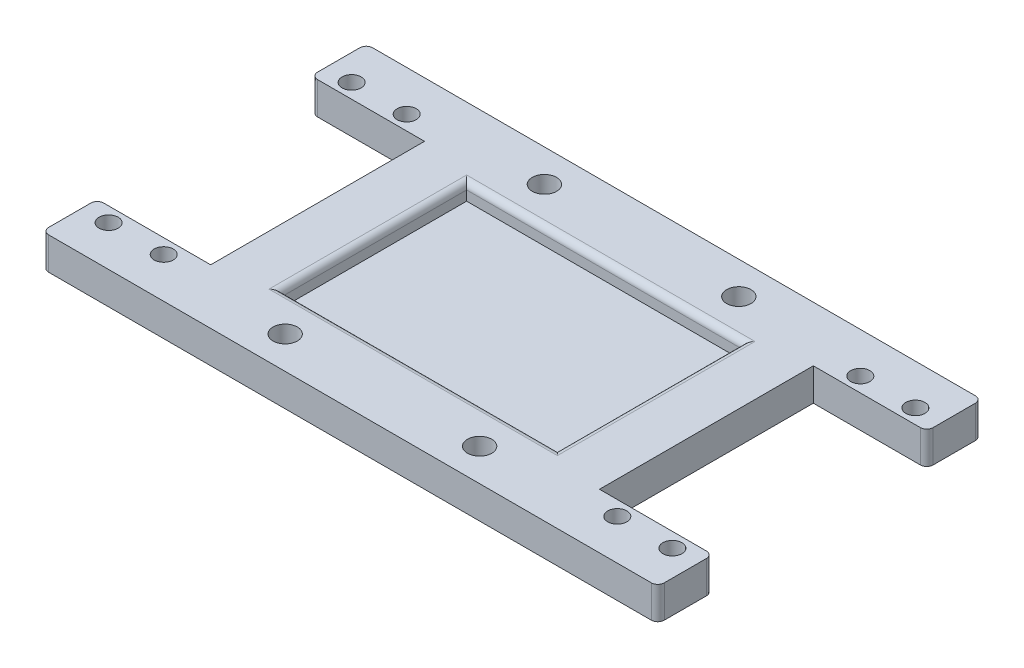
SolidWorks part; units mm, degrees
ref_plane "Front Plane" through (0, 0, 0) normal (0, 0, 1) x (1, 0, 0)
ref_plane "Top Plane" through (0, 0, 0) normal (0, 1, 0) x (1, 0, 0)
ref_plane "Right Plane" through (0, 0, 0) normal (1, 0, 0) x (0, 0, -1)
sketch "Sketch1" plane through (0, 0, 0) normal (0, 1, 0) x (1, 0, 0)
  line L1 (-60, -50) -> (60, -50)
  line L2 (-60, -50) -> (-60, 50)
  line L3 (-60, 50) -> (60, 50)
  line L4 (60, -50) -> (60, 50)
  line L5 (-60, -50) -> (60, 50) construction
  line L6 (-60, 50) -> (60, -50) construction
  point P0 (0, 0)
  dimension "D1" = 100
  dimension "D2" = 120
extrude "Boss-Extrude1" add sketch "Sketch1" along normal blind 5
sketch "Sketch2" plane through (0, 5, 0) normal (0, 1, 0) x (1, 0, 0)
  line L1 (-42.5, -28.5) -> (42.5, -28.5)
  line L2 (-42.5, -28.5) -> (-42.5, 28.5)
  line L3 (-42.5, 28.5) -> (42.5, 28.5)
  line L4 (42.5, -28.5) -> (42.5, 28.5)
  line L5 (-42.5, -28.5) -> (42.5, 28.5) construction
  line L6 (-42.5, 28.5) -> (42.5, -28.5) construction
  line L7 (-60, -50) -> (60, -50)
  line L8 (-60, -50) -> (-60, 50)
  line L9 (-60, 50) -> (60, 50)
  line L10 (60, -50) -> (60, 50)
  line L11 (-60, -50) -> (60, 50) construction
  line L12 (-60, 50) -> (60, -50) construction
  point P0 (0, 0)
  point P6 (0, 0)
  dimension "D1" = 85
  dimension "D2" = 57
extrude "Boss-Extrude2" add sketch "Sketch2" along normal blind 5
sketch "Sketch3" plane through (0, 0, 0) normal (0, -1, 0) x (1, 0, 0)
  line L0 (0, -55) -> (0, 55) construction
  line L1 (60, 50) -> (95, 50)
  line L2 (60, 50) -> (60, 33)
  line L3 (60, 33) -> (95, 33)
  line L4 (95, 50) -> (95, 33)
  line L5 (60, -50) -> (95, -50)
  line L6 (60, -50) -> (60, -33)
  line L7 (60, -33) -> (95, -33)
  line L8 (95, -50) -> (95, -33)
  line L9 (-95, -50) -> (-95, -33)
  line L10 (-60, -33) -> (-95, -33)
  line L11 (-60, -50) -> (-60, -33)
  line L12 (-60, -50) -> (-95, -50)
  line L13 (-95, 50) -> (-95, 33)
  line L14 (-60, 33) -> (-95, 33)
  line L15 (-60, 50) -> (-60, 33)
  line L16 (-60, 50) -> (-95, 50)
  dimension "D1" = 66
  dimension "D2" = 35
extrude "Boss-Extrude3" add sketch "Sketch3" against normal up to surface (10 mm away) up to face at (0, 10, 0)
sketch "Sketch4" plane through (0, 0, 0) normal (0, -1, 0) x (1, 0, 0)
  line L0 (70, 37.5) -> (70, -37.5) construction
  line L1 (60, 33) -> (60, -33) construction
  line L2 (0, -5.5) -> (0, 5.5) construction
  line L3 (-70, 37.5) -> (-70, -37.5) construction
  circle A0 centre (70, 37.5) radius 2.95
  circle A1 centre (87, 37.5) radius 2.95
  circle A2 centre (70, -37.5) radius 2.95
  circle A3 centre (87, -37.5) radius 2.95
  circle A4 centre (-87, -37.5) radius 2.95
  circle A5 centre (-70, -37.5) radius 2.95
  circle A6 centre (-87, 37.5) radius 2.95
  circle A7 centre (-70, 37.5) radius 2.95
  point P8 (70, 0)
  dimension "D3" = 5.9
  dimension "D1" = 75
  dimension "D2" = 17
  dimension "D4" = 10
extrude "Cut-Extrude1" cut sketch "Sketch4" against normal through all both and the other way through all
fillet "Fillet1" radius 2 12 edges at (42.5, 10, 0) (0, 10, -28.5) (-42.5, 10, 0) (0, 10, 28.5) (-95, 5, 50) (-95, 5, 33) (-95, 5, -33) (-95, 5, -50) (95, 5, -50) (95, 5, -33) (95, 5, 50) (95, 5, 33)
sketch "Sketch5" plane through (0, 10, 0) normal (0, 1, 0) x (1, 0, 0)
  line L1 (-30, -40) -> (30, -40) construction
  line L2 (-30, -40) -> (-30, 40) construction
  line L3 (-30, 40) -> (30, 40) construction
  line L4 (30, -40) -> (30, 40) construction
  line L5 (-30, -40) -> (30, 40) construction
  line L6 (-30, 40) -> (30, -40) construction
  circle A0 centre (-30, 40) radius 3.75
  circle A1 centre (30, 40) radius 3.75
  circle A2 centre (-30, -40) radius 3.75
  circle A3 centre (30, -40) radius 3.75
  point P0 (0, 0)
  dimension "D3" = 7.5
  dimension "D1" = 80
  dimension "D2" = 60
extrude "Cut-Extrude2" cut sketch "Sketch5" against normal through all both and the other way through all
